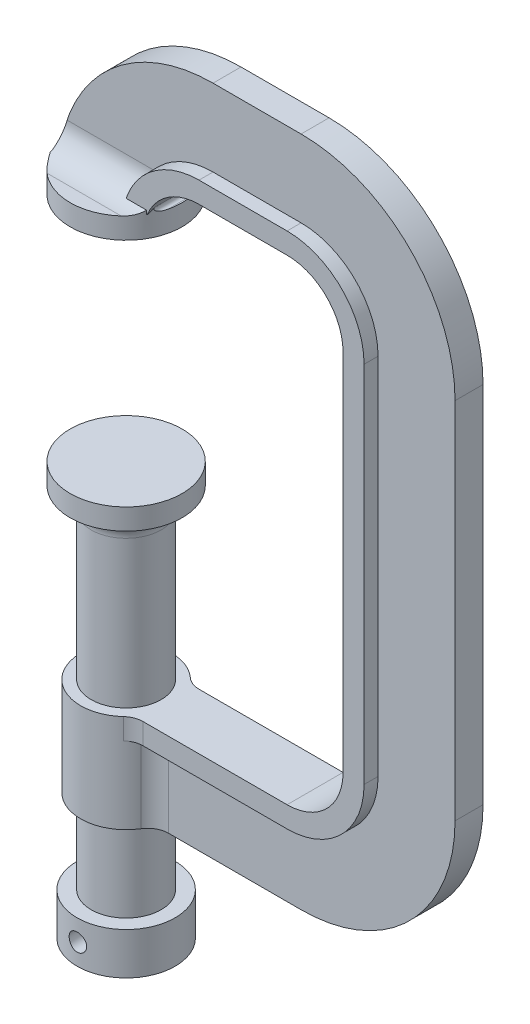
SolidWorks part; units mm, degrees
ref_plane "Front Plane" through (0, 0, 0) normal (0, 0, 1) x (1, 0, 0)
ref_plane "Top Plane" through (0, 0, 0) normal (0, 1, 0) x (1, 0, 0)
ref_plane "Right Plane" through (0, 0, 0) normal (1, 0, 0) x (0, 0, -1)
sketch "Sketch2" plane through (0, 0, 0) normal (0, 0, 1) x (1, 0, 0)
  line L0 (0, 14) -> (27, 14)
  line L1 (35, 22) -> (35, 74)
  line L2 (27, 82) -> (14.4162, 82)
  line L3 (-4.1329, 77) -> (2.1565, 77) construction
  arc A0 (35, 74) -> (27, 82) centre (27, 74) ccw
  arc A1 (35, 22) -> (27, 14) centre (27, 22) cw
  arc A2 (14.4162, 82) -> (7, 77) centre (14.4162, 74) ccw
  dimension "D1" = 8
  dimension "D2" = 8
  dimension "D3" = 8
  dimension "D4" = 35
  dimension "D5" = 14
  dimension "D6" = 63
  dimension "D7" = 5
  dimension "D8" = 7
sketch "Sketch4" plane through (0, 0, 0) normal (1, 0, 0) x (0, 0, -1)
  line L0 (-2, 0) -> (2, 0)
  line L1 (2, 0) -> (2, 11)
  line L2 (2, 11) -> (4, 11)
  line L3 (4, 11) -> (4, 14)
  line L4 (4, 14) -> (-4, 14)
  line L5 (-4, 14) -> (-4, 11)
  line L6 (-4, 11) -> (-2, 11)
  line L7 (-2, 11) -> (-2, 0)
  line L8 (0, -2.9648) -> (0, 19.8429) construction
  line L9 (0, 22) -> (0, 14) construction
  dimension "D1" = 4
  dimension "D2" = 8
  dimension "D3" = 3
sweep "Sweep1" add profiles "Sketch4" path "Sketch2"
sketch "Sketch5" plane through (0, 0, 0) normal (0, 1, 0) x (1, 0, 0)
  circle A0 centre (0, 0) radius 6.5
  dimension "D1" = 13
extrude "Extrude1" add sketch "Sketch5" along normal up to surface (14 mm away) up to face at (13.5, 14, 0)
sketch "Sketch6" plane through (27.7522, 68.6053, 0) normal (-0.375, -0.927, 0) x (0.927, -0.375, 0)
  line L0 (-22.3858, 9.2349) -> (-22.3858, -7.8416) construction
  line L8 (-25.3858, 2) -> (-36.3858, 2)
  line L9 (-36.3858, 2) -> (-36.3858, -2)
  line L10 (-36.3858, -2) -> (-25.3858, -2)
  line L11 (-25.3858, -2) -> (-25.3858, -4)
  line L12 (-25.3858, -4) -> (-22.3858, -4)
  line L13 (-22.3858, -4) -> (-22.3858, 4)
  line L14 (-22.3858, 4) -> (-25.3858, 4)
  line L15 (-25.3858, 4) -> (-25.3858, 2)
  line L16 (-25.3858, 2) -> (-36.3858, 2)
  line L17 (-36.3858, 2) -> (-36.3858, -2)
  line L18 (-36.3858, -2) -> (-25.3858, -2)
  line L19 (-25.3858, -2) -> (-25.3858, -4)
  line L20 (-25.3858, -4) -> (-22.3858, -4)
  line L21 (-22.3858, -4) -> (-22.3858, 4)
  line L22 (-22.3858, 4) -> (-25.3858, 4)
  line L23 (-25.3858, 4) -> (-25.3858, 2)
  dimension "D1" = 0
revolve "Revolve1" add sketch "Sketch6" angle 22.024 about L0
ref_plane "Plane1" through (0, 74, 0) normal (0, 1, 0) x (-1, 0, 0)
sketch "Sketch8" plane through (0, 74, 0) normal (0, 1, 0) x (-1, 0, 0)
  circle A0 centre (0, 0) radius 8
  dimension "D1" = 16
extrude "Extrude2" add sketch "Sketch8" along normal up to surface (3 mm away)
fillet "Fillet1" radius 3 4 edges at (5.1235, 12.5, -4) (6.1847, 5.5, -2) (5.1235, 12.5, 4) (6.1847, 5.5, 2)
fillet "Fillet3" radius 4 2 edges at (-1.5, 77, -2) (-1.5, 77, 2)
fillet "Fillet4" radius 1 1 edges at (-7, 77.0001, 0)
fillet "Fillet5" radius 0.5 1 edges at (7, 77, 0)
sketch "Sketch9" plane through (0, 0, 0) normal (0, 0, 1) x (1, 0, 0)
  line L0 (0, 51.9307) -> (0, -6.0298) construction
  line L1 (0, 41) -> (8, 41)
  line L2 (8, 41) -> (8, 38)
  line L3 (8, 38) -> (5, 38)
  line L4 (5, 38) -> (5, -12)
  line L5 (5, -12) -> (7, -12)
  line L6 (7, -12) -> (7, -18)
  line L7 (7, -18) -> (0, -18)
  line L8 (0, -18) -> (0, 41)
  line L9 (27, 14) -> (6.4226, 14) construction
  line L10 (27, 0) -> (8.0777, 0) construction
  dimension "D1" = 16
  dimension "D2" = 10
  dimension "D3" = 3
  dimension "D4" = 14
  dimension "D5" = 24
  dimension "D6" = 12
  dimension "D7" = 6
revolve "Revolve2" add sketch "Sketch9" angle 360 about L0
fillet "Fillet6" radius 3 1 edges at (0, 38, 5)
sketch "Sketch10" plane through (0, 0, 0) normal (0, 0, 1) x (1, 0, 0)
  line L5 (9.0437, -15) -> (-9.6099, -15) construction
  circle A0 centre (0, -15) radius 1.25
  dimension "D1" = 2.5
extrude "Cut-Extrude1" cut sketch "Sketch10" against normal through all and the other way through all
